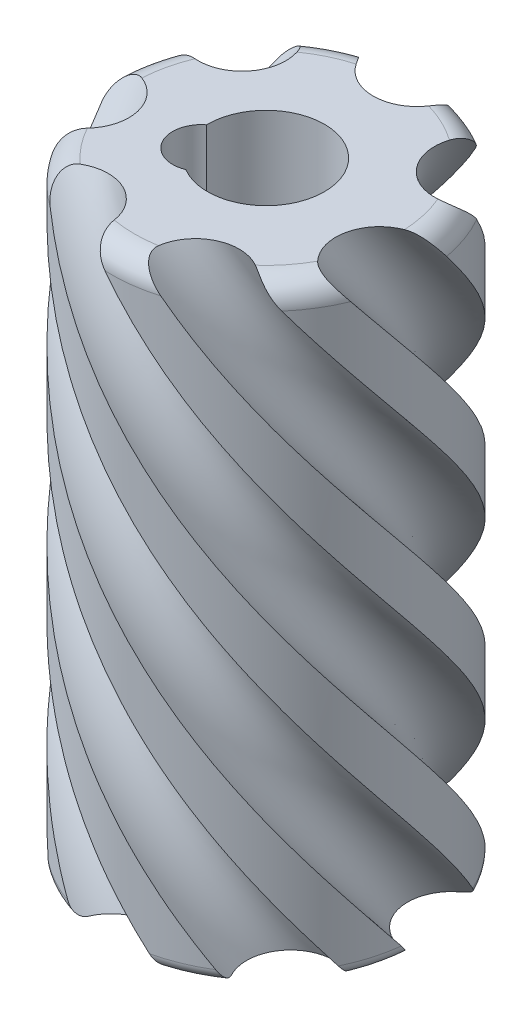
SolidWorks part; units mm, degrees
note: '?' marks a value the reader was unsure of.
ref_plane "Front Plane" through (0, 0, 0) normal (0, 0, 1) x (1, 0, 0)
ref_plane "Top Plane" through (0, 0, 0) normal (0, 1, 0) x (1, 0, 0)
ref_plane "Right Plane" through (0, 0, 0) normal (1, 0, 0) x (0, 0, -1)
sketch "Sketch4" plane through (0, 0, 0) normal (0, 1, 0) x (1, 0, 0)
  circle A0 centre (0, 0) radius 6.625
  dimension "D1" = 13.25
extrude "Boss-Extrude3" add sketch "Sketch4" along normal blind 26
sketch "Sketch2" plane through (0, 0, 0) normal (0, 1, 0) x (-1, 0, 0)
  circle A0 centre (0, 0) radius 2.8
  dimension "D1" = 5.6
fillet "Fillet1" radius 1 1 edges at (0, 26, 6.625)
sketch "Sketch3" plane through (0, 0, 0) normal (0, -1, 0) x (1, 0, 0)
  circle A0 centre (0, 0) radius 1.25
  dimension "D1" = 2.5
extrude "Cut-Extrude3" cut sketch "Sketch3" against normal blind 20
extrude "Cut-Extrude4" cut sketch "Sketch2" along normal blind 5.5
ref_axis "Axis2" through (0, 5.5, 0) along (0, -1, 0)?
sketch "Sketch30" plane through (0, 0, 0) normal (0, 1, 0) x (1, 0, 0)
  circle A0 centre (0, -0.0831) radius 3.9169
curve "Helix/Spiral2" pitch 52 height 26 turns 0.5
sketch "Sketch32" plane through (0, 0, 0) normal (0, 1, 0) x (1, 0, 0)
  circle A0 centre (0, -6.625) radius 1.875
  circle A2 centre (0, 0) radius 6.625 construction
  dimension "D1" = 3.75
sweep "Cut-Sweep3" cut profiles "Sketch32" path "Helix/Spiral2"
pattern_circular "CirPattern1" count 7 over 360 about axis through (0, 5.5, 0) along (0, -1, 0) of "Cut-Sweep3"
sketch "Sketch33" plane through (0, 26, 0) normal (0, 1, 0) x (1, 0, 0)
  circle A0 centre (0, 0) radius 2.5
  dimension "D1" = 5
extrude "Cut-Extrude5" cut sketch "Sketch33" against normal blind 5.5
fillet "Fillet3" radius 0.5 7 edges at (-2.8745, 0, 5.9689) (-6.4589, 0, 1.4742) (-5.1796, 0, -4.1306) (0, 0, -6.625) (5.1796, 0, -4.1306) (6.4589, 0, 1.4742) (2.8745, 0, 5.9689)
sketch "Sketch34" plane through (0, 5.5, 0) normal (0, -1, 0) x (1, 0, 0)
  line L1 (-1.1691, 2.025) -> (-2.3383, 0)
  line L2 (-2.3383, 0) -> (-1.1691, -2.025)
  line L3 (-1.1691, -2.025) -> (1.1691, -2.025)
  line L4 (1.1691, -2.025) -> (2.3383, 0)
  line L5 (2.3383, 0) -> (1.1691, 2.025)
  line L6 (1.1691, 2.025) -> (-1.1691, 2.025)
  circle A0 centre (0, 0) radius 2.025 construction
  dimension "D1" = 4.05
extrude "Cut-Extrude6" cut sketch "Sketch34" against normal blind 16
chamfer "Chamfer3" distance 0.7 angle 55 2 edges at (0, 5.5, 2.8) (0, 20.5, 2.5)
sketch "Sketch35" plane through (0, 26, 0) normal (0, 1, 0) x (1, 0, 0)
  circle A0 centre (-1.7537, -1.0125) radius 1.225
extrude "Cut-Extrude7" cut sketch "Sketch35" against normal blind 26
scale "Scale1" scale about centroid uniform scaling yes scale factor 1.3
